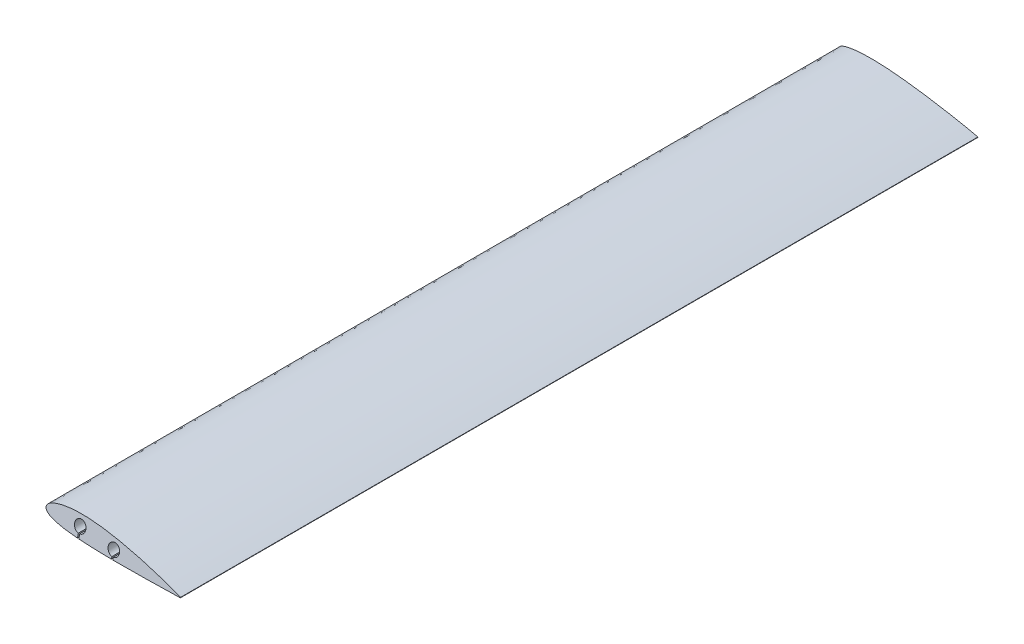
SolidWorks part; units mm, degrees
material "Custom Plastic"
ref_plane "Front Plane" through (0, 0, 0) normal (0, 0, 1) x (1, 0, 0)
ref_plane "Top Plane" through (0, 0, 0) normal (0, 1, 0) x (1, 0, 0)
ref_plane "Right Plane" through (0, 0, 0) normal (1, 0, 0) x (0, 0, -1)
curve "Curve1"
  spline degree 3 poles (119.72, -8.1948, 0) (119.6176, -8.1622, 0) (119.1985, -8.0289, 0) (118.2498, -7.745, 0) (116.6764, -7.2682, 0) (114.4937, -6.6229, 0) (111.726, -5.8198, 0) (108.3989, -4.8842, 0) (104.5474, -3.8358, 0) (100.2105, -2.7001, 0) (95.4335, -1.5003, 0) (90.2667, -0.2644, 0) (84.7642, 0.9828, 0) (78.9848, 2.2132, 0) (72.9906, 3.4008, 0) (66.8472, 4.5234, 0) (60.6201, 5.5483, 0) (54.3772, 6.4571, 0) (48.1692, 7.2302, 0) (42.0621, 7.8148, 0) (36.1259, 8.1773, 0) (30.4496, 8.3149, 0) (25.1001, 8.227, 0) (20.1405, 7.9255, 0) (15.6293, 7.4181, 0) (11.6181, 6.7322, 0) (8.1521, 5.8882, 0) (5.2655, 4.9177, 0) (2.98, 3.8441, 0) (1.3063, 2.6841, 0) (0.2335, 1.4154, 0) (-0.1257, -0.004, 0) (0.316, -1.3971, 0) (1.4469, -2.6023, 0) (3.1553, -3.6733, 0) (5.4426, -4.65, 0) (8.2964, -5.5286, 0) (11.6917, -6.304, 0) (15.5927, -6.9754, 0) (19.9599, -7.5398, 0) (24.7472, -8.002, 0) (29.9056, -8.3725, 0) (35.3823, -8.6597, 0) (41.1213, -8.8812, 0) (47.0817, -9.0555, 0) (53.2028, -9.1881, 0) (59.4204, -9.2536, 0) (65.6487, -9.2717, 0) (71.8184, -9.2592, 0) (77.8616, -9.2203, 0) (83.7119, -9.1645, 0) (89.3044, -9.1004, 0) (94.5769, -9.0293, 0) (99.4704, -8.9537, 0) (103.9296, -8.8805, 0) (107.904, -8.8075, 0) (111.3483, -8.7373, 0) (114.2228, -8.6769, 0) (116.4943, -8.6239, 0) (118.1358, -8.5859, 0) (119.1326, -8.5579, 0) (119.5801, -8.549, 0) (119.6954, -8.5467, 0) knots 0 0 0 0 0.001308 0.005358 0.012063 0.021337 0.033087 0.047171 0.063441 0.081714 0.101785 0.123442 0.146433 0.170517 0.195424 0.220875 0.246594 0.272302 0.297725 0.322799 0.347029 0.370162 0.391954 0.412188 0.43067 0.447231 0.461732 0.474085 0.484276 0.492392 0.498749 0.5041 0.509453 0.51579 0.523838 0.533885 0.546005 0.560171 0.576284 0.594211 0.613803 0.634869 0.65721 0.680611 0.704835 0.729853 0.755197 0.780583 0.805729 0.830359 0.854204 0.877002 0.898494 0.918443 0.936623 0.952826 0.966868 0.978592 0.987852 0.994547 0.998596 1 1 1 1
sketch "Sketch4" plane through (0, 0, 0) normal (0, 0, 1) x (1, 0, 0)
  line L0 (119.72, -8.1948) -> (119.6954, -8.5467)
  line L1 (0, 0) -> (162.2931, 0) construction
  spline S2 degree 3 poles (1370.0357, 3790.6471) (156.0859, -40.1115) (140.424, -14.3791) (118.2498, -7.745) (116.6764, -7.2682) (114.4937, -6.6229) (111.726, -5.8198) (108.3989, -4.8842) (104.5474, -3.8358) (100.2105, -2.7001) (95.4335, -1.5003) (90.2667, -0.2644) (84.7642, 0.9828) (78.9848, 2.2132) (72.9906, 3.4008) (66.8472, 4.5234) (60.6201, 5.5483) (54.3772, 6.4571) (48.1692, 7.2302) (42.0621, 7.8148) (36.1259, 8.1773) (30.4496, 8.3149) (25.1001, 8.227) (20.1405, 7.9255) (15.6293, 7.4181) (11.6181, 6.7322) (8.1521, 5.8882) (5.2655, 4.9177) (2.98, 3.8441) (1.3063, 2.6841) (0.2335, 1.4154) (-0.1257, -0.004) (0.316, -1.3971) (1.4469, -2.6023) (3.1553, -3.6733) (5.4426, -4.65) (8.2964, -5.5286) (11.6917, -6.304) (15.5927, -6.9754) (19.9599, -7.5398) (24.7472, -8.002) (29.9056, -8.3725) (35.3823, -8.6597) (41.1213, -8.8812) (47.0817, -9.0555) (53.2028, -9.1881) (59.4204, -9.2536) (65.6487, -9.2717) (71.8184, -9.2592) (77.8616, -9.2203) (83.7119, -9.1645) (89.3044, -9.1004) (94.5769, -9.0293) (99.4704, -8.9537) (103.9296, -8.8805) (107.904, -8.8075) (111.3483, -8.7373) (114.2228, -8.6769) (116.4943, -8.6239) (118.1358, -8.5859) (148.3455, -7.7372) (178.3806, -23.1567) (115.1651, 3990.3657) knots -0.26989 -0.26989 -0.26989 -0.26989 0.001308 0.005358 0.012063 0.021337 0.033087 0.047171 0.063441 0.081714 0.101785 0.123442 0.146433 0.170517 0.195424 0.220875 0.246594 0.272302 0.297725 0.322799 0.347029 0.370162 0.391954 0.412188 0.43067 0.447231 0.461732 0.474085 0.484276 0.492392 0.498749 0.5041 0.509453 0.51579 0.523838 0.533885 0.546005 0.560171 0.576284 0.594211 0.613803 0.634869 0.65721 0.680611 0.704835 0.729853 0.755197 0.780583 0.805729 0.830359 0.854204 0.877002 0.898494 0.918443 0.936623 0.952826 0.966868 0.978592 0.987852 0.994547 0.998596 1.35602 1.35602 1.35602 1.35602 only from (119.72, -8.1948) to (119.6954, -8.5467)
  spline S3 degree 3 poles (119.72, -8.1948) (119.6176, -8.1622) (119.1985, -8.0289) (118.2498, -7.745) (116.6764, -7.2682) (114.4937, -6.6229) (111.726, -5.8198) (108.3989, -4.8842) (104.5474, -3.8358) (100.2105, -2.7001) (95.4335, -1.5003) (90.2667, -0.2644) (84.7642, 0.9828) (78.9848, 2.2132) (72.9906, 3.4008) (66.8472, 4.5234) (60.6201, 5.5483) (54.3772, 6.4571) (48.1692, 7.2302) (42.0621, 7.8148) (36.1259, 8.1773) (30.4496, 8.3149) (25.1001, 8.227) (20.1405, 7.9255) (15.6293, 7.4181) (11.6181, 6.7322) (8.1521, 5.8882) (5.2655, 4.9177) (2.98, 3.8441) (1.3063, 2.6841) (0.2335, 1.4154) (-0.1257, -0.004) (0.316, -1.3971) (1.4469, -2.6023) (3.1553, -3.6733) (5.4426, -4.65) (8.2964, -5.5286) (11.6917, -6.304) (15.5927, -6.9754) (19.9599, -7.5398) (24.7472, -8.002) (29.9056, -8.3725) (35.3823, -8.6597) (41.1213, -8.8812) (47.0817, -9.0555) (53.2028, -9.1881) (59.4204, -9.2536) (65.6487, -9.2717) (71.8184, -9.2592) (77.8616, -9.2203) (83.7119, -9.1645) (89.3044, -9.1004) (94.5769, -9.0293) (99.4704, -8.9537) (103.9296, -8.8805) (107.904, -8.8075) (111.3483, -8.7373) (114.2228, -8.6769) (116.4943, -8.6239) (118.1358, -8.5859) (119.1326, -8.5579) (119.5801, -8.549) (119.6954, -8.5467) knots 0 0 0 0 0.001308 0.005358 0.012063 0.021337 0.033087 0.047171 0.063441 0.081714 0.101785 0.123442 0.146433 0.170517 0.195424 0.220875 0.246594 0.272302 0.297725 0.322799 0.347029 0.370162 0.391954 0.412188 0.43067 0.447231 0.461732 0.474085 0.484276 0.492392 0.498749 0.5041 0.509453 0.51579 0.523838 0.533885 0.546005 0.560171 0.576284 0.594211 0.613803 0.634869 0.65721 0.680611 0.704835 0.729853 0.755197 0.780583 0.805729 0.830359 0.854204 0.877002 0.898494 0.918443 0.936623 0.952826 0.966868 0.978592 0.987852 0.994547 0.998596 1 1 1 1
  dimension "D1" = 0
extrude "Boss-Extrude2" add sketch "Sketch4" along normal mid plane 700
sketch "Sketch5" plane through (0, 0, -350) normal (0, 0, -1) x (-1, 0, 0)
  line L1 (-30, 0) -> (-29.4, 0) construction
  line L2 (-29.4, 0) -> (-29.4, -8.3234)
  line L3 (-30, 0) -> (-30.6, 0) construction
  line L4 (-30.6, 0) -> (-30.6, -8.3975)
  line L5 (-60, -2.5) -> (-59.4, -2.5) construction
  line L6 (-119.72, -8.1948) -> (-119.6954, -8.5467)
  line L7 (-119.72, -8.1948) -> (-119.6954, -8.5467)
  line L8 (-59.4, -2.5) -> (-59.4, -9.2455)
  line L9 (-60, -2.5) -> (-60.6, -2.5) construction
  line L10 (-60.6, -2.5) -> (-60.6, -9.2528)
  circle A0 centre (-30, 0) radius 4.75 construction
  circle A1 centre (-60, -2.5) radius 4.95
  circle A2 centre (-30, 0) radius 4.95
  circle A4 centre (-60, -2.5) radius 4.75 construction
  spline S0 degree 3 poles (-119.72, -8.1948) (-119.6176, -8.1622) (-119.1985, -8.0289) (-118.2498, -7.745) (-116.6764, -7.2682) (-114.4937, -6.6229) (-111.726, -5.8198) (-108.3989, -4.8842) (-104.5474, -3.8358) (-100.2105, -2.7001) (-95.4335, -1.5003) (-90.2667, -0.2644) (-84.7642, 0.9828) (-78.9848, 2.2132) (-72.9906, 3.4008) (-66.8472, 4.5234) (-60.6201, 5.5483) (-54.3772, 6.4571) (-48.1692, 7.2302) (-42.0621, 7.8148) (-36.1259, 8.1773) (-30.4496, 8.3149) (-25.1001, 8.227) (-20.1405, 7.9255) (-15.6293, 7.4181) (-11.6181, 6.7322) (-8.1521, 5.8882) (-5.2655, 4.9177) (-2.98, 3.8441) (-1.3063, 2.6841) (-0.2335, 1.4154) (0.1257, -0.004) (-0.316, -1.3971) (-1.4469, -2.6023) (-3.1553, -3.6733) (-5.4426, -4.65) (-8.2964, -5.5286) (-11.6917, -6.304) (-15.5927, -6.9754) (-19.9599, -7.5398) (-24.7472, -8.002) (-29.9056, -8.3725) (-35.3823, -8.6597) (-41.1213, -8.8812) (-47.0817, -9.0555) (-53.2028, -9.1881) (-59.4204, -9.2536) (-65.6487, -9.2717) (-71.8184, -9.2592) (-77.8616, -9.2203) (-83.7119, -9.1645) (-89.3044, -9.1004) (-94.5769, -9.0293) (-99.4704, -8.9537) (-103.9296, -8.8805) (-107.904, -8.8075) (-111.3483, -8.7373) (-114.2228, -8.6769) (-116.4943, -8.6239) (-118.1358, -8.5859) (-119.1326, -8.5579) (-119.5801, -8.549) (-119.6954, -8.5467) knots 0 0 0 0 0.001308 0.005358 0.012063 0.021337 0.033087 0.047171 0.063441 0.081714 0.101785 0.123442 0.146433 0.170517 0.195424 0.220875 0.246594 0.272302 0.297725 0.322799 0.347029 0.370162 0.391954 0.412188 0.43067 0.447231 0.461732 0.474085 0.484276 0.492392 0.498749 0.5041 0.509453 0.51579 0.523838 0.533885 0.546005 0.560171 0.576284 0.594211 0.613803 0.634869 0.65721 0.680611 0.704835 0.729853 0.755197 0.780583 0.805729 0.830359 0.854204 0.877002 0.898494 0.918443 0.936623 0.952826 0.966868 0.978592 0.987852 0.994547 0.998596 1 1 1 1 construction
  spline S3 degree 3 poles (-115.1725, 3989.8946) (-178.3782, -23.1555) (-148.3443, -7.7372) (-118.1358, -8.5859) (-116.4943, -8.6239) (-114.2228, -8.6769) (-111.3483, -8.7373) (-107.904, -8.8075) (-103.9296, -8.8805) (-99.4704, -8.9537) (-94.5769, -9.0293) (-89.3044, -9.1004) (-83.7119, -9.1645) (-77.8616, -9.2203) (-71.8184, -9.2592) (-65.6487, -9.2717) (-59.4204, -9.2536) (-53.2028, -9.1881) (-47.0817, -9.0555) (-41.1213, -8.8812) (-35.3823, -8.6597) (-29.9056, -8.3725) (-24.7472, -8.002) (-19.9599, -7.5398) (-15.5927, -6.9754) (-11.6917, -6.304) (-8.2964, -5.5286) (-5.4426, -4.65) (-3.1553, -3.6733) (-1.4469, -2.6023) (-0.316, -1.3971) (0.1257, -0.004) (-0.2335, 1.4154) (-1.3063, 2.6841) (-2.98, 3.8441) (-5.2655, 4.9177) (-8.1521, 5.8882) (-11.6181, 6.7322) (-15.6293, 7.4181) (-20.1405, 7.9255) (-25.1001, 8.227) (-30.4496, 8.3149) (-36.1259, 8.1773) (-42.0621, 7.8148) (-48.1692, 7.2302) (-54.3772, 6.4571) (-60.6201, 5.5483) (-66.8472, 4.5234) (-72.9906, 3.4008) (-78.9848, 2.2132) (-84.7642, 0.9828) (-90.2667, -0.2644) (-95.4335, -1.5003) (-100.2105, -2.7001) (-104.5474, -3.8358) (-108.3989, -4.8842) (-111.726, -5.8198) (-114.4937, -6.6229) (-116.6764, -7.2682) (-118.2498, -7.745) (-140.4231, -14.3788) (-156.0845, -40.1093) (-1369.8814, 3790.1602) knots -0.356006 -0.356006 -0.356006 -0.356006 0.001404 0.005453 0.012148 0.021408 0.033132 0.047174 0.063377 0.081557 0.101506 0.122998 0.145796 0.169641 0.194271 0.219417 0.244803 0.270147 0.295165 0.319389 0.34279 0.365131 0.386197 0.405789 0.423716 0.439829 0.453995 0.466115 0.476162 0.48421 0.490547 0.4959 0.501251 0.507608 0.515724 0.525915 0.538268 0.552769 0.56933 0.587812 0.608046 0.629838 0.652971 0.677201 0.702275 0.727698 0.753406 0.779125 0.804576 0.829483 0.853567 0.876558 0.898215 0.918286 0.936559 0.952829 0.966913 0.978663 0.987937 0.994642 0.998692 1.269879 1.269879 1.269879 1.269879 only from (-119.6954, -8.5467) to (-119.72, -8.1948)
  spline S4 degree 3 poles (-119.6954, -8.5467) (-119.5801, -8.549) (-119.1326, -8.5579) (-118.1358, -8.5859) (-116.4943, -8.6239) (-114.2228, -8.6769) (-111.3483, -8.7373) (-107.904, -8.8075) (-103.9296, -8.8805) (-99.4704, -8.9537) (-94.5769, -9.0293) (-89.3044, -9.1004) (-83.7119, -9.1645) (-77.8616, -9.2203) (-71.8184, -9.2592) (-65.6487, -9.2717) (-59.4204, -9.2536) (-53.2028, -9.1881) (-47.0817, -9.0555) (-41.1213, -8.8812) (-35.3823, -8.6597) (-29.9056, -8.3725) (-24.7472, -8.002) (-19.9599, -7.5398) (-15.5927, -6.9754) (-11.6917, -6.304) (-8.2964, -5.5286) (-5.4426, -4.65) (-3.1553, -3.6733) (-1.4469, -2.6023) (-0.316, -1.3971) (0.1257, -0.004) (-0.2335, 1.4154) (-1.3063, 2.6841) (-2.98, 3.8441) (-5.2655, 4.9177) (-8.1521, 5.8882) (-11.6181, 6.7322) (-15.6293, 7.4181) (-20.1405, 7.9255) (-25.1001, 8.227) (-30.4496, 8.3149) (-36.1259, 8.1773) (-42.0621, 7.8148) (-48.1692, 7.2302) (-54.3772, 6.4571) (-60.6201, 5.5483) (-66.8472, 4.5234) (-72.9906, 3.4008) (-78.9848, 2.2132) (-84.7642, 0.9828) (-90.2667, -0.2644) (-95.4335, -1.5003) (-100.2105, -2.7001) (-104.5474, -3.8358) (-108.3989, -4.8842) (-111.726, -5.8198) (-114.4937, -6.6229) (-116.6764, -7.2682) (-118.2498, -7.745) (-119.1985, -8.0289) (-119.6176, -8.1622) (-119.72, -8.1948) knots 0 0 0 0 0.001404 0.005453 0.012148 0.021408 0.033132 0.047174 0.063377 0.081557 0.101506 0.122998 0.145796 0.169641 0.194271 0.219417 0.244803 0.270147 0.295165 0.319389 0.34279 0.365131 0.386197 0.405789 0.423716 0.439829 0.453995 0.466115 0.476162 0.48421 0.490547 0.4959 0.501251 0.507608 0.515724 0.525915 0.538268 0.552769 0.56933 0.587812 0.608046 0.629838 0.652971 0.677201 0.702275 0.727698 0.753406 0.779125 0.804576 0.829483 0.853567 0.876558 0.898215 0.918286 0.936559 0.952829 0.966913 0.978663 0.987937 0.994642 0.998692 1 1 1 1
  spline M6 degree 3 poles (-119.6954, -8.5467) (-119.5801, -8.549) (-119.1326, -8.5579) (-118.1358, -8.5859) (-116.4943, -8.6239) (-114.2228, -8.6769) (-111.3483, -8.7373) (-107.904, -8.8075) (-103.9296, -8.8805) (-99.4704, -8.9537) (-94.5769, -9.0293) (-89.3044, -9.1004) (-83.7119, -9.1645) (-77.8616, -9.2203) (-71.8184, -9.2592) (-65.6487, -9.2717) (-59.4204, -9.2536) (-53.2028, -9.1881) (-47.0817, -9.0555) (-41.1213, -8.8812) (-35.3823, -8.6597) (-29.9056, -8.3725) (-24.7472, -8.002) (-19.9599, -7.5398) (-15.5927, -6.9754) (-11.6917, -6.304) (-8.2964, -5.5286) (-5.4426, -4.65) (-3.1553, -3.6733) (-1.4469, -2.6023) (-0.316, -1.3971) (0.1257, -0.004) (-0.2335, 1.4154) (-1.3063, 2.6841) (-2.98, 3.8441) (-5.2655, 4.9177) (-8.1521, 5.8882) (-11.6181, 6.7322) (-15.6293, 7.4181) (-20.1405, 7.9255) (-25.1001, 8.227) (-30.4496, 8.3149) (-36.1259, 8.1773) (-42.0621, 7.8148) (-48.1692, 7.2302) (-54.3772, 6.4571) (-60.6201, 5.5483) (-66.8472, 4.5234) (-72.9906, 3.4008) (-78.9848, 2.2132) (-84.7642, 0.9828) (-90.2667, -0.2644) (-95.4335, -1.5003) (-100.2105, -2.7001) (-104.5474, -3.8358) (-108.3989, -4.8842) (-111.726, -5.8198) (-114.4937, -6.6229) (-116.6764, -7.2682) (-118.2498, -7.745) (-119.1985, -8.0289) (-119.6176, -8.1622) (-119.72, -8.1948) knots 0 0 0 0 0.001404 0.005453 0.012148 0.021408 0.033132 0.047174 0.063377 0.081557 0.101506 0.122998 0.145796 0.169641 0.194271 0.219417 0.244803 0.270147 0.295165 0.319389 0.34279 0.365131 0.386197 0.405789 0.423716 0.439829 0.453995 0.466115 0.476162 0.48421 0.490547 0.4959 0.501251 0.507608 0.515724 0.525915 0.538268 0.552769 0.56933 0.587812 0.608046 0.629838 0.652971 0.677201 0.702275 0.727698 0.753406 0.779125 0.804576 0.829483 0.853567 0.876558 0.898215 0.918286 0.936559 0.952829 0.966913 0.978663 0.987937 0.994642 0.998692 1 1 1 1
  dimension "D1" = 9.5
  dimension "D6" = 0.2
  dimension "D12" = 9.5
  dimension "D2" = 0.6
  dimension "D3" = 0.6
  dimension "D4" = 30
  dimension "D8" = 30
  dimension "D9" = 2.5
  dimension "D10" = 0.6
  dimension "D11" = 0.6
  dimension "D5" = 0
  dimension "D7" = 0.2
extrude "Cut-Extrude1" cut sketch "Sketch5" against normal through all contours A1 | A1 L10 L8 M6 | A2 | A2 L4 L2 M6 region at (30.0022, -6.6494, -350) region at (30, 0, -350) region at (60.0004, -8.3435, -350) region at (60, -2.5, -350)
sketch "Sketch6" plane through (0, 0, 0) normal (1, 0, 0) x (0, 0, -1)
  line L0 (350, -9.5) -> (345.1227, 12.5)
  line L1 (345.1227, 12.5) -> (350, 12.5)
  line L2 (350, 12.5) -> (350, -9.5)
  line L3 (350, 0) -> (352.9573, 0) construction
  dimension "D1" = 12.5
  dimension "D2" = 22
  dimension "D3" = 9.5
extrude "Cut-Extrude2" cut sketch "Sketch6" along normal through all both and the other way through all
mirror "Mirror1" about plane through (0, 0, 0) normal (0, 0, 1) of "Cut-Extrude2"
sketch "Sketch7" plane through (0, 0, 0) normal (0, 0, 1) x (1, 0, 0)
  line L0 (0, 0) -> (119.7077, -8.3708)
  line L1 (119.72, -8.1948) -> (119.6954, -8.5467) construction
sketch "Sketch1" plane through (0, 0, 0) normal (0, 0, 1) x (1, 0, 0)
  line L0 (0, 0) -> (-120, 0)
  spline S0 degree 3 poles (-120, 0) (-86.4181, 33.0029) (-44.1117, 7.7348) (0, 0) knots 0 0 0 0 1 1 1 1
  dimension "D1" = 120
sketch "Sketch10" plane through (0, 73.5132, -331.5964) normal (0, 0.2164, -0.9763) x (-1, 0, 0)
  line L10 (-29.4, -80.3308) -> (-29.4, -83.8235)
  line L11 (-119.72, -83.6918) -> (-119.6954, -84.0523)
  line L12 (-60.6, -84.7754) -> (-60.6, -82.8915)
  line L13 (-59.4, -82.8915) -> (-59.4, -84.768)
  line L14 (-30.6, -83.8994) -> (-30.6, -80.3308)
  line L15 (-29.4, -80.3308) -> (-29.4, -83.8235)
  line L16 (-119.72, -83.6918) -> (-119.6954, -84.0523)
  line L17 (-60.6, -84.7754) -> (-60.6, -82.8915)
  line L18 (-59.4, -82.8915) -> (-59.4, -84.768)
  line L19 (-30.6, -83.8994) -> (-30.6, -80.3308)
  ellipse E4 centre (-30, -75.298) end of major axis (-30, -80.3682) minor radius 4.95 (-29.4, -80.3308) -> (-30.6, -80.3308) ccw
  ellipse E5 centre (-60, -77.8587) end of major axis (-60, -82.9289) minor radius 4.95 (-59.4, -82.8915) -> (-60.6, -82.8915) ccw
  ellipse E6 centre (-30, -75.298) end of major axis (-30, -80.3682) minor radius 4.95 (-29.4, -80.3308) -> (-30.6, -80.3308) ccw
  ellipse E7 centre (-60, -77.8587) end of major axis (-60, -82.9289) minor radius 4.95 (-59.4, -82.8915) -> (-60.6, -82.8915) ccw
  spline S6 degree 3 poles (-129.0038, -3067.1467) (-294.6774, 64.5062) (-148.6922, -98.237) (-17.9123, -82.7534) (-16.2774, -82.5299) (-13.0267, -81.9958) (-11.4096, -81.6863) (-9.0051, -81.1129) (-8.2061, -80.9027) (-6.6242, -80.4309) (-5.8432, -80.169) (-4.6937, -79.7184) (-4.3144, -79.5582) (-3.5663, -79.2103) (-3.1961, -79.0219) (-2.4776, -78.6127) (-2.13, -78.3914) (-1.6362, -78.0203) (-1.4761, -77.8901) (-1.1671, -77.6141) (-1.0176, -77.4673) (-0.7415, -77.1576) (-0.6143, -76.9942) (-0.3882, -76.6449) (-0.2903, -76.4593) (-0.1348, -76.0775) (-0.0757, -75.8799) (-0.0026, -75.4686) (0.009, -75.2604) (-0.0187, -74.85) (-0.0572, -74.6439) (-0.1751, -74.2444) (-0.2536, -74.0525) (-0.4465, -73.6832) (-0.5601, -73.5076) (-0.8084, -73.1781) (-0.9439, -73.0226) (-1.2314, -72.7252) (-1.3839, -72.5827) (-1.6973, -72.3124) (-1.8588, -72.1844) (-2.355, -71.8179) (-2.7013, -71.5968) (-3.413, -71.1833) (-3.7803, -70.9912) (-4.5232, -70.6346) (-4.8987, -70.47) (-6.0342, -70.005) (-6.803, -69.7345) (-8.3571, -69.2478) (-9.9271, -68.8138) (-11.5221, -68.463) (-13.1272, -68.1454) (-13.9353, -68.0034) (-17.9689, -67.3685) (-21.1974, -67.085) (-27.6561, -66.7928) (-30.8863, -66.7855) (-37.3484, -66.9826) (-40.5801, -67.1867) (-45.4286, -67.6248) (-47.046, -67.7927) (-50.2759, -68.1647) (-51.887, -68.3684) (-56.7111, -69.0208) (-59.9156, -69.5084) (-66.3051, -70.5725) (-69.4897, -71.1507) (-75.8419, -72.3842) (-79.0098, -73.0386) (-88.4895, -75.1104) (-94.778, -76.6335) (-104.1669, -79.1183) (-107.289, -79.9805) (-111.9602, -81.3289) (-113.5149, -81.7888) (-115.8444, -82.4906) (-116.6204, -82.7271) (-117.7833, -83.0861) (-118.1709, -83.2061) (-156.859, -95.1146) (-191.3126, -124.403) (407.6713, -3035.1854) knots -2.402462 -2.402462 -2.402462 -2.402462 0.0625 0.0625 0.09375 0.09375 0.125 0.125 0.140625 0.140625 0.15625 0.15625 0.164063 0.164063 0.171875 0.171875 0.179688 0.179688 0.183594 0.183594 0.1875 0.1875 0.191406 0.191406 0.195313 0.195313 0.199219 0.199219 0.203125 0.203125 0.207031 0.207031 0.210938 0.210938 0.214844 0.214844 0.21875 0.21875 0.222656 0.222656 0.226563 0.226563 0.234375 0.234375 0.242188 0.242188 0.25 0.25 0.265625 0.265625 0.28125 0.296875 0.296875 0.3125 0.3125 0.375 0.375 0.4375 0.4375 0.5 0.5 0.53125 0.53125 0.5625 0.5625 0.625 0.625 0.6875 0.6875 0.75 0.75 0.875 0.875 0.9375 0.9375 0.96875 0.96875 0.984375 0.984375 0.992188 0.992188 1.763921 1.763921 1.763921 1.763921 only from (-29.4, -83.8235) to (-119.72, -83.6918)
  spline S7 degree 3 poles (-285.2311, -3077.69) (-204.8189, -68.0593) (-161.4186, -82.9984) (-117.2335, -84.1142) (-116.618, -84.1285) (-114.7715, -84.1723) (-113.5405, -84.2002) (-109.8475, -84.2794) (-107.3854, -84.3298) (-99.999, -84.4648) (-95.0746, -84.5421) (-85.2255, -84.671) (-80.3008, -84.7244) (190.96, -86.5516) (458.0708, -25.0124) (758.3092, 2743.6823) knots -2.180934 -2.180934 -2.180934 -2.180934 0.03125 0.03125 0.0625 0.0625 0.125 0.125 0.25 0.25 0.5 0.5 0.75 0.75 14.269732 14.269732 14.269732 14.269732 only from (-119.6954, -84.0523) to (-60.6, -84.7754)
  spline S8 degree 3 poles (-580.6833, -3000.2145) (-466.5066, 26.805) (-257.5568, -88.4357) (-49.7952, -84.636) (-47.3948, -84.5775) (-42.5946, -84.4391) (-40.1949, -84.3584) (107.3754, -78.3122) (250.5806, -7.1829) (308.8579, 2879.7851) knots -21.134089 -21.134089 -21.134089 -21.134089 0.25 0.25 0.5 0.5 0.75 0.75 15.876916 15.876916 15.876916 15.876916 only from (-59.4, -84.768) to (-30.6, -83.8994)
  spline S9 degree 3 poles (-29.4, -83.8235) (-26.1092, -83.6082) (-22.8239, -83.335) (-17.9123, -82.7534) (-16.2774, -82.5299) (-13.0267, -81.9958) (-11.4096, -81.6863) (-9.0051, -81.1129) (-8.2061, -80.9027) (-6.6242, -80.4309) (-5.8432, -80.169) (-4.6937, -79.7184) (-4.3144, -79.5582) (-3.5663, -79.2103) (-3.1961, -79.0219) (-2.4776, -78.6127) (-2.13, -78.3914) (-1.6362, -78.0203) (-1.4761, -77.8901) (-1.1671, -77.6141) (-1.0176, -77.4673) (-0.7415, -77.1576) (-0.6143, -76.9942) (-0.3882, -76.6449) (-0.2903, -76.4593) (-0.1348, -76.0775) (-0.0757, -75.8799) (-0.0026, -75.4686) (0.009, -75.2604) (-0.0187, -74.85) (-0.0572, -74.6439) (-0.1751, -74.2444) (-0.2536, -74.0525) (-0.4465, -73.6832) (-0.5601, -73.5076) (-0.8084, -73.1781) (-0.9439, -73.0226) (-1.2314, -72.7252) (-1.3839, -72.5827) (-1.6973, -72.3124) (-1.8588, -72.1844) (-2.355, -71.8179) (-2.7013, -71.5968) (-3.413, -71.1833) (-3.7803, -70.9912) (-4.5232, -70.6346) (-4.8987, -70.47) (-6.0342, -70.005) (-6.803, -69.7345) (-8.3571, -69.2478) (-9.9271, -68.8138) (-11.5221, -68.463) (-13.1272, -68.1454) (-13.9353, -68.0034) (-17.9689, -67.3685) (-21.1974, -67.085) (-27.6561, -66.7928) (-30.8863, -66.7855) (-37.3484, -66.9826) (-40.5801, -67.1867) (-45.4286, -67.6248) (-47.046, -67.7927) (-50.2759, -68.1647) (-51.887, -68.3684) (-56.7111, -69.0208) (-59.9156, -69.5084) (-66.3051, -70.5725) (-69.4897, -71.1507) (-75.8419, -72.3842) (-79.0098, -73.0386) (-88.4895, -75.1104) (-94.778, -76.6335) (-104.1669, -79.1183) (-107.289, -79.9805) (-111.9602, -81.3289) (-113.5149, -81.7888) (-115.8444, -82.4906) (-116.6204, -82.7271) (-117.7833, -83.0861) (-118.1709, -83.2061) (-118.9464, -83.4448) (-119.3337, -83.5659) (-119.72, -83.6918) knots 0 0 0 0 0.0625 0.0625 0.09375 0.09375 0.125 0.125 0.140625 0.140625 0.15625 0.15625 0.164063 0.164063 0.171875 0.171875 0.179688 0.179688 0.183594 0.183594 0.1875 0.1875 0.191406 0.191406 0.195313 0.195313 0.199219 0.199219 0.203125 0.203125 0.207031 0.207031 0.210938 0.210938 0.214844 0.214844 0.21875 0.21875 0.222656 0.222656 0.226563 0.226563 0.234375 0.234375 0.242188 0.242188 0.25 0.25 0.265625 0.265625 0.28125 0.296875 0.296875 0.3125 0.3125 0.375 0.375 0.4375 0.4375 0.5 0.5 0.53125 0.53125 0.5625 0.5625 0.625 0.625 0.6875 0.6875 0.75 0.75 0.875 0.875 0.9375 0.9375 0.96875 0.96875 0.984375 0.984375 0.992188 0.992188 1 1 1 1
  spline S10 degree 3 poles (-119.6954, -84.0523) (-119.0799, -84.0648) (-118.4644, -84.0831) (-117.2335, -84.1142) (-116.618, -84.1285) (-114.7715, -84.1723) (-113.5405, -84.2002) (-109.8475, -84.2794) (-107.3854, -84.3298) (-99.999, -84.4648) (-95.0746, -84.5421) (-85.2255, -84.671) (-80.3008, -84.7244) (-70.4509, -84.7908) (-65.5257, -84.8023) (-60.6, -84.7754) knots 0 0 0 0 0.03125 0.03125 0.0625 0.0625 0.125 0.125 0.25 0.25 0.5 0.5 0.75 0.75 1 1 1 1
  spline S11 degree 3 poles (-59.4, -84.768) (-56.9983, -84.7514) (-54.597, -84.7238) (-49.7952, -84.636) (-47.3948, -84.5775) (-42.5946, -84.4391) (-40.1949, -84.3584) (-35.3965, -84.1618) (-32.9978, -84.0457) (-30.6, -83.8994) knots 0 0 0 0 0.25 0.25 0.5 0.5 0.75 0.75 1 1 1 1
  dimension "D1" = 0
sketch "Sketch11" plane through (0, 73.5132, -331.5964) normal (0, 0.2164, -0.9763) x (-1, 0, 0)
  line L0 (-119.7077, -83.872) -> (-0.006, -75.0392) construction
  line L1 (-119.72, -83.6918) -> (-119.6954, -84.0523) construction
  spline S0 degree 3 poles (-29.4, -83.8235) (-26.1092, -83.6082) (-22.8239, -83.335) (-17.9123, -82.7534) (-16.2774, -82.5299) (-13.0267, -81.9958) (-11.4096, -81.6863) (-9.0051, -81.1129) (-8.2061, -80.9027) (-6.6242, -80.4309) (-5.8432, -80.169) (-4.6937, -79.7184) (-4.3144, -79.5582) (-3.5663, -79.2103) (-3.1961, -79.0219) (-2.4776, -78.6127) (-2.13, -78.3914) (-1.6362, -78.0203) (-1.4761, -77.8901) (-1.1671, -77.6141) (-1.0176, -77.4673) (-0.7415, -77.1576) (-0.6143, -76.9942) (-0.3882, -76.6449) (-0.2903, -76.4593) (-0.1348, -76.0775) (-0.0757, -75.8799) (-0.0026, -75.4686) (0.009, -75.2604) (-0.0187, -74.85) (-0.0572, -74.6439) (-0.1751, -74.2444) (-0.2536, -74.0525) (-0.4465, -73.6832) (-0.5601, -73.5076) (-0.8084, -73.1781) (-0.9439, -73.0226) (-1.2314, -72.7252) (-1.3839, -72.5827) (-1.6973, -72.3124) (-1.8588, -72.1844) (-2.355, -71.8179) (-2.7013, -71.5968) (-3.413, -71.1833) (-3.7803, -70.9912) (-4.5232, -70.6346) (-4.8987, -70.47) (-6.0342, -70.005) (-6.803, -69.7345) (-8.3571, -69.2478) (-9.9271, -68.8138) (-11.5221, -68.463) (-13.1272, -68.1454) (-13.9353, -68.0034) (-17.9689, -67.3685) (-21.1974, -67.085) (-27.6561, -66.7928) (-30.8863, -66.7855) (-37.3484, -66.9826) (-40.5801, -67.1867) (-45.4286, -67.6248) (-47.046, -67.7927) (-50.2759, -68.1647) (-51.887, -68.3684) (-56.7111, -69.0208) (-59.9156, -69.5084) (-66.3051, -70.5725) (-69.4897, -71.1507) (-75.8419, -72.3842) (-79.0098, -73.0386) (-88.4895, -75.1104) (-94.778, -76.6335) (-104.1669, -79.1183) (-107.289, -79.9805) (-111.9602, -81.3289) (-113.5149, -81.7888) (-115.8444, -82.4906) (-116.6204, -82.7271) (-117.7833, -83.0861) (-118.1709, -83.2061) (-118.9464, -83.4448) (-119.3337, -83.5659) (-119.72, -83.6918) knots 0 0 0 0 0.0625 0.0625 0.09375 0.09375 0.125 0.125 0.140625 0.140625 0.15625 0.15625 0.164063 0.164063 0.171875 0.171875 0.179688 0.179688 0.183594 0.183594 0.1875 0.1875 0.191406 0.191406 0.195313 0.195313 0.199219 0.199219 0.203125 0.203125 0.207031 0.207031 0.210938 0.210938 0.214844 0.214844 0.21875 0.21875 0.222656 0.222656 0.226563 0.226563 0.234375 0.234375 0.242188 0.242188 0.25 0.25 0.265625 0.265625 0.28125 0.296875 0.296875 0.3125 0.3125 0.375 0.375 0.4375 0.4375 0.5 0.5 0.53125 0.53125 0.5625 0.5625 0.625 0.625 0.6875 0.6875 0.75 0.75 0.875 0.875 0.9375 0.9375 0.96875 0.96875 0.984375 0.984375 0.992188 0.992188 1 1 1 1 construction
sketch "Sketch12" plane through (0, 73.5132, 331.5964) normal (0, 0.2164, 0.9763) x (1, 0, 0)
  line L0 (119.7077, -83.872) -> (0.006, -75.0393) construction
  line L1 (119.72, -83.6918) -> (119.6954, -84.0523) construction
  spline S0 degree 3 poles (29.4, -83.8235) (26.129, -83.6095) (22.8643, -83.3382) (17.9857, -82.7629) (16.3627, -82.5421) (13.9352, -82.1459) (13.1273, -82.0027) (11.5145, -81.6884) (10.7088, -81.5174) (9.1076, -81.1389) (8.3118, -80.9314) (6.7338, -80.466) (5.9506, -80.2066) (4.4199, -79.615) (3.6713, -79.282) (2.5933, -78.6826) (2.2393, -78.4639) (1.5735, -77.9802) (1.2597, -77.7172) (0.6953, -77.1209) (0.4441, -76.7781) (0.1832, -76.2124) (0.1134, -76.0126) (0.0205, -75.6085) (-0.0036, -75.4033) (0.002, -74.9852) (0.0309, -74.7767) (0.1305, -74.3732) (0.2024, -74.1741) (0.3801, -73.7982) (0.4861, -73.6204) (0.7252, -73.281) (0.8592, -73.1188) (1.2823, -72.6614) (1.5929, -72.3893) (2.2518, -71.8879) (2.6018, -71.6592) (3.6676, -71.028) (4.4077, -70.6759) (5.9208, -70.0472) (6.694, -69.7715) (8.264, -69.2745) (9.0592, -69.053) (11.4451, -68.4568) (13.0459, -68.1456) (17.8681, -67.3802) (21.109, -67.0908) (25.9953, -66.867) (27.6282, -66.8279) (30.9015, -66.8121) (32.5335, -66.8353) (37.4159, -66.9856) (40.6537, -67.1922) (47.1016, -67.7772) (50.3117, -68.1552) (56.7142, -69.0214) (59.9069, -69.5072) (66.2781, -70.5678) (69.4561, -71.1445) (75.7997, -72.3757) (78.9654, -73.0293) (88.4447, -75.0999) (94.741, -76.6241) (104.1526, -79.1144) (107.2816, -79.9784) (111.9584, -81.3284) (113.5143, -81.7886) (115.8448, -82.4907) (116.6209, -82.7272) (117.7839, -83.0863) (118.1714, -83.2062) (118.9469, -83.4449) (119.3341, -83.566) (119.72, -83.6918) knots 0 0 0 0 0.0625 0.0625 0.09375 0.09375 0.109375 0.109375 0.125 0.125 0.140625 0.140625 0.15625 0.15625 0.171875 0.171875 0.179688 0.179688 0.1875 0.1875 0.195313 0.195313 0.199219 0.199219 0.203125 0.203125 0.207031 0.207031 0.210938 0.210938 0.214844 0.214844 0.21875 0.21875 0.226563 0.226563 0.234375 0.234375 0.25 0.25 0.265625 0.265625 0.28125 0.28125 0.3125 0.3125 0.375 0.375 0.40625 0.40625 0.4375 0.4375 0.5 0.5 0.5625 0.5625 0.625 0.625 0.6875 0.6875 0.75 0.75 0.875 0.875 0.9375 0.9375 0.96875 0.96875 0.984375 0.984375 0.992188 0.992188 1 1 1 1 construction
sketch "Sketch13" plane through (0, 0, 0) normal (0, 0, 1) x (1, 0, 0)
  line L0 (119.7077, -8.3708) -> (0, 0)
